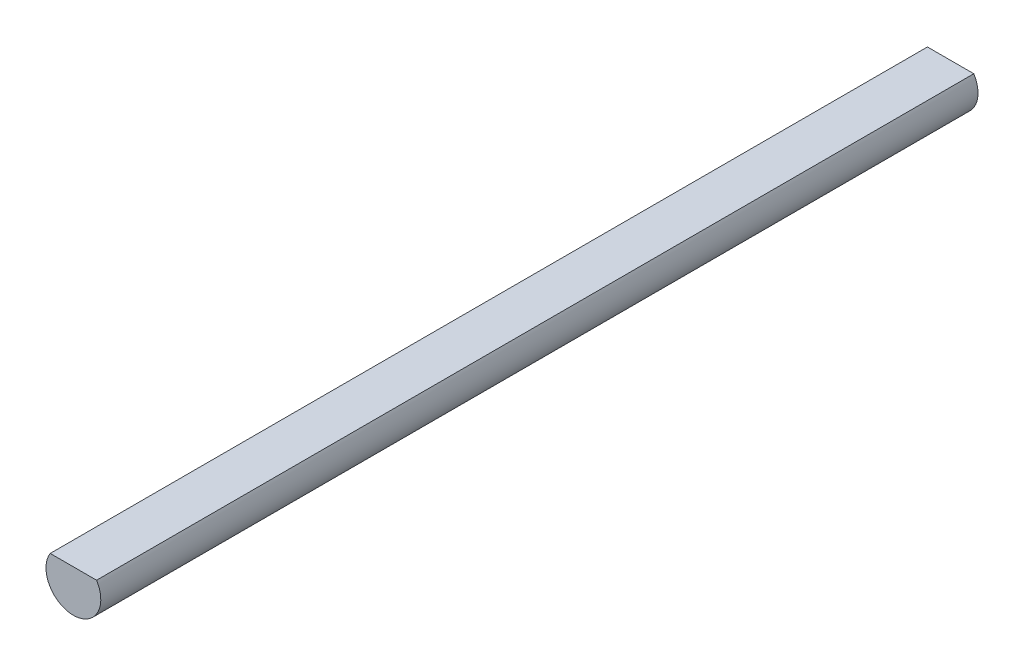
SolidWorks part; units mm, degrees
ref_plane "Front Plane" through (0, 0, 0) normal (0, 0, 1) x (1, 0, 0)
ref_plane "Top Plane" through (0, 0, 0) normal (0, 1, 0) x (1, 0, 0)
ref_plane "Right Plane" through (0, 0, 0) normal (1, 0, 0) x (0, 0, -1)
sketch "Sketch1" plane through (0, 0, 0) normal (0, 0, 1) x (1, 0, 0)
  circle A0 centre (0, 0) radius 1.875
  dimension "D1" = 3.75
extrude "Boss-Extrude1" add sketch "Sketch1" along normal blind 60
sketch "Sketch2" plane through (0, 0, 0) normal (0, 0, -1) x (-1, 0, 0)
  point P0 (0, 0)
  point P4 (0, 0)
  point P5 (0, 0)
sketch "Sketch3" plane through (0, 0, 60) normal (0, 0, 1) x (1, 0, 0)
  line L1 (-1.7321, 1) -> (1.7321, 1)
  arc A2 (1.7321, 1) -> (-1.7321, 1) centre (0, 0) ccw
  dimension "D2" = 4
  dimension "D1" = 1
extrude "Cut-Extrude1" cut sketch "Sketch3" against normal through all
